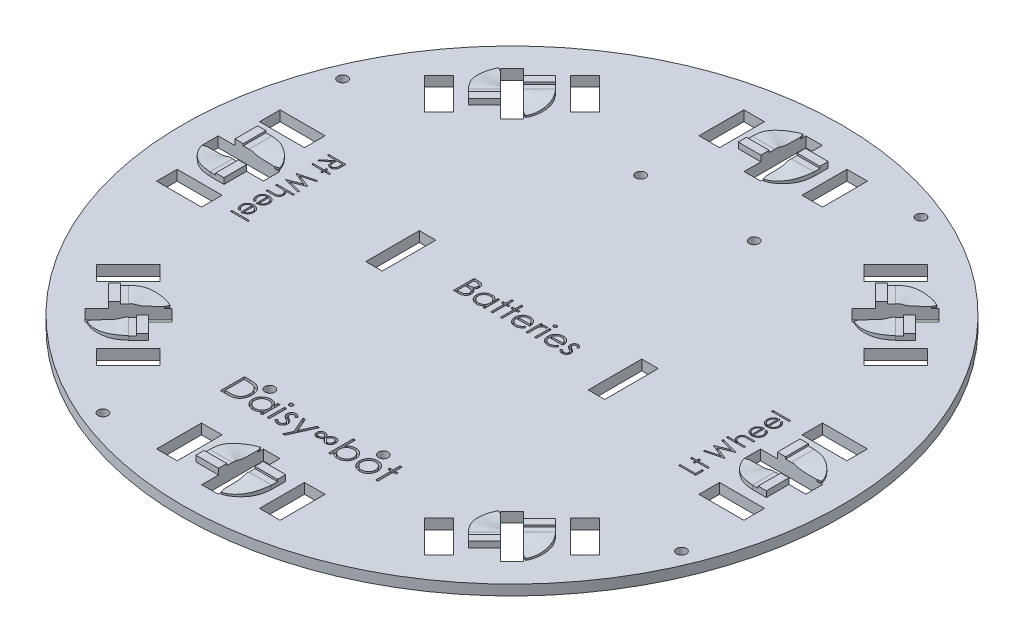
SolidWorks part; units mm, degrees
ref_plane "Front" through (0, 0, 0) normal (0, 0, 1) x (1, 0, 0)
ref_plane "Top" through (0, 0, 0) normal (0, 1, 0) x (1, 0, 0)
ref_plane "Right" through (0, 0, 0) normal (1, 0, 0) x (0, 0, -1)
sketch "Sketch1" plane through (0, 0, 0) normal (0, 1, 0) x (1, 0, 0)
  circle A0 centre (0, 0) radius 101.6
  dimension "D1" = 203.2
extrude "Boss-Extrude1" add sketch "Sketch1" along normal blind 3.175 contours A0
sketch "Sketch2" plane through (0, 3.175, 0) normal (0, 1, 0) x (1, 0, 0)
  line L1 (-2.54, -93.1333) -> (2.54, -93.1333)
  line L2 (-2.54, -93.1333) -> (-2.54, -74.0833)
  line L3 (-2.54, -74.0833) -> (2.54, -74.0833)
  line L4 (2.54, -93.1333) -> (2.54, -74.0833)
  circle A0 centre (0, 0) radius 101.6 construction
  point P4 (0, -74.0833)
  dimension "D1" = 5.08
  dimension "D2" = 19.05
  dimension "D3" = 93.1333
extrude "Cut-Extrude1" cut sketch "Sketch2" against normal up to next and the other way through all contours L1 L4 L3 L2
sketch "Sketch4" plane through (0, 3.175, 0) normal (0, 1, 0) x (1, 0, 0)
  line L0 (0, -83.6083) -> (-2.9434, -74.5495) construction
  line L1 (-2.9434, -74.5495) -> (0, -83.6083) construction
  line L2 (0, -83.6083) -> (-5.5987, -75.9025) construction
  line L3 (0, -83.6083) -> (-7.7059, -78.0097) construction
  line L4 (0, -83.6083) -> (-9.0588, -80.665) construction
  line L5 (0, -83.6083) -> (-9.525, -83.6083) construction
  line L9 (2.54, -74.0833) -> (-2.54, -74.0833) construction
  line L10 (2.54, -74.0833) -> (2.54, -93.1333) construction
  line L11 (-2.54, -74.0833) -> (-2.54, -93.1333) construction
  line L12 (2.54, -93.1333) -> (-2.54, -93.1333) construction
  circle A0 centre (0, -83.6083) radius 9.525 construction
  point P16 (0, -74.0833)
  point P19 (2.54, -83.6083)
  dimension "D1" = 18
  dimension "D2" = 18
  dimension "D3" = 18
  dimension "D4" = 18
  dimension "D5" = 18
ref_plane "Plane1" through (-24.5719, 0, 7.9839) normal (0.9511, 0, -0.309) x (-0.309, 0, -0.9511)
ref_plane "Plane2" through (-39.7581, 0, 28.886) normal (0.809, 0, -0.5878) x (-0.5878, 0, -0.809)
ref_plane "Plane3" through (-39.7581, 0, 54.7224) normal (0.5878, 0, -0.809) x (-0.809, 0, -0.5878)
ref_plane "Plane4" through (-24.5719, 0, 75.6245) normal (0.309, 0, -0.9511) x (-0.9511, 0, -0.309)
ref_plane "Plane5" through (0, 0, 83.6083) normal (0, 0, -1) x (-1, 0, 0)
sketch "Sketch5" plane through (-24.5719, 0, 7.9839) normal (0.9511, 0, -0.309) x (-0.309, 0, -0.9511)
  line L0 (-69.6725, 3.175) -> (-87.7902, 3.175) construction
  line L1 (-71.2966, 3.175) -> (-69.9913, 3.175)
  line L2 (-71.2966, 3.175) -> (-71.2966, 3.683)
  line L3 (-71.2966, 3.683) -> (-69.9913, 3.683)
  line L4 (-69.9913, 3.175) -> (-69.9913, 3.683)
  dimension "D2" = 0.508
sketch "Sketch6" plane through (-39.7581, 0, 28.886) normal (0.809, 0, -0.5878) x (-0.5878, 0, -0.809)
  line L0 (-58.4417, 3.175) -> (-73.8535, 3.175) construction
  line L1 (-63.3193, 3.175) -> (-58.1156, 3.175)
  line L2 (-63.3193, 3.175) -> (-63.3193, 3.775)
  line L3 (-63.3193, 3.775) -> (-58.1156, 3.775)
  line L4 (-58.1156, 3.175) -> (-58.1156, 3.775)
  dimension "D2" = 0.6
sketch "Sketch7" plane through (-39.7581, 0, 54.7224) normal (0.5878, 0, -0.809) x (-0.809, 0, -0.5878)
  line L0 (-41.4902, 3.175) -> (-52.6875, 3.175) construction
  line L1 (-46.0041, 3.175) -> (-39.6188, 3.175)
  line L2 (-46.0041, 3.175) -> (-46.0041, 4.075)
  line L3 (-46.0041, 4.075) -> (-39.6188, 4.075)
  line L4 (-39.6188, 3.175) -> (-39.6188, 4.075)
  dimension "D2" = 0.9
sketch "Sketch10" plane through (-24.5719, 0, 75.6245) normal (0.309, 0, -0.9511) x (-0.9511, 0, -0.309)
  line L0 (-25.8364, 3.175) -> (-16.7776, 3.175) construction
  line L1 (-23.1657, 3.175) -> (-16.3114, 3.175)
  line L2 (-23.1657, 3.175) -> (-23.1657, 4.375)
  line L3 (-23.1657, 4.375) -> (-16.3114, 4.375)
  line L4 (-16.3114, 3.175) -> (-16.3114, 4.375)
  dimension "D3" = 1.2
sketch "Sketch11" plane through (0, 0, 83.6083) normal (0, 0, -1) x (-1, 0, 0)
  line L0 (0, 3.175) -> (9.525, 3.175) construction
  line L1 (2.54, 3.175) -> (9.525, 3.175)
  line L2 (2.54, 3.175) -> (2.54, 4.375)
  line L3 (2.54, 4.375) -> (9.525, 4.375)
  line L4 (9.525, 3.175) -> (9.525, 4.375)
  dimension "D3" = 1.2
loft "Loft1" add profiles "Sketch5", "Sketch6", "Sketch7", "Sketch10", "Sketch11" connector at (-2.54, 3.683, 75.791) connector at (-2.54, 3.775, 80.1123) connector at (-2.54, 4.075, 81.7629) connector at (-2.54, 4.375, 82.783) connector at (-2.54, 4.375, 83.6083)
sketch "Sketch13" plane through (-104.9799, 0, 83.6083) normal (0, 0, -1) x (-1, 0, 0)
  line L6 (-95.4549, 3.175) -> (-102.4399, 3.175)
  line L7 (-95.4549, 3.175) -> (-95.4549, 4.375)
  line L8 (-95.4549, 4.375) -> (-102.4399, 4.375)
  line L9 (-102.4399, 3.175) -> (-102.4399, 4.375)
extrude "Boss-Extrude4" add sketch "Sketch13" against normal blind 1.7907
sketch "Sketch25" plane through (0, 0, 85.399) normal (0, 0, 1) x (1, 0, 0)
  line L0 (-9.525, 4.375) -> (-2.54, 4.375) construction
  line L1 (-9.525, 3.175) -> (-2.54, 3.175)
  line L2 (-9.525, 3.175) -> (-9.525, 4.975)
  line L3 (-9.525, 4.975) -> (-2.54, 4.975)
  line L4 (-2.54, 3.175) -> (-2.54, 4.975)
  dimension "D1" = 0.6
extrude "Boss-Extrude5" add sketch "Sketch25" along normal blind 2.54
sketch "Sketch14" plane through (-2.54, 0, 0) normal (1, 0, 0) x (0, 0, -1)
  line L0 (-83.6083, 3.175) -> (-83.6083, 0) construction
  line L1 (-74.0833, 0) -> (-93.1333, 0) construction
ref_plane "Plane6" through (0, 0, 0) normal (1, 0, 0) x (0, 0, -1)
sketch "Sketch15" plane through (0, 0, 0) normal (1, 0, 0) x (0, 0, -1)
  line L0 (-83.6083, 0) -> (-83.6083, 3.175) construction
pattern_circular "CirPattern1" count 2 over 360 about axis through (0, 0, 83.6083) along (0, 1, 0) of "Loft1", "Boss-Extrude5", "Boss-Extrude4" reverse direction yes
ref_axis "Axis1" through (0, 50, 0) along (0, -1, 0)
pattern_circular "CirPattern5" count 8 over 360 about axis through (0, 50, 0) along (0, -1, 0) of "CirPattern1", "Cut-Extrude1"
sketch "Sketch18" plane through (0, 3.175, 0) normal (0, 1, 0) x (1, 0, 0)
  line L4 (0, -101.6) -> (0, 101.6) construction
  line L5 (0, -1.7463) -> (0, 1.7463) construction
  line L6 (-101.6, 0) -> (101.6, 0) construction
  circle A8 centre (0, 0) radius 101.6 construction
sketch "Sketch19" plane through (0, 3.175, 0) normal (0, 1, 0) x (1, 0, 0)
  line L0 (-36.9366, -89.1729) -> (0, 0) construction
  line L1 (0, -101.6) -> (0, 101.6) construction
  circle A1 centre (-36.9366, -89.1729) radius 1.5
  dimension "D1" = 96.52
  dimension "D4" = 3
  dimension "D5" = 22.5
extrude "Cut-Extrude2" cut sketch "Sketch19" against normal through all
pattern_circular "CirPattern7" count 4 over 360 about axis through (0, 50, 0) along (0, -1, 0) of "Cut-Extrude2"
sketch "Sketch23" plane through (0, 3.175, 0) normal (0, 1, 0) x (1, 0, 0)
  line L9 (-2.54, -87.939) -> (-2.54, -93.1333) construction
  line L10 (-19.05, -76.6805) -> (-12.7, -76.6805)
  line L11 (-19.05, -76.6805) -> (-19.05, -90.5362)
  line L16 (-19.05, -90.5362) -> (-12.7, -90.5362)
  line L17 (-12.7, -76.6805) -> (-12.7, -90.5362)
  line L19 (2.54, -74.0833) -> (2.54, -79.2776) construction
  line L20 (0, -50) -> (0, 50) construction
  line L21 (12.7, -76.6805) -> (12.7, -90.5362)
  line L22 (19.05, -90.5362) -> (12.7, -90.5362)
  line L23 (19.05, -76.6805) -> (19.05, -90.5362)
  line L24 (19.05, -76.6805) -> (12.7, -76.6805)
  point P8 (-2.54, -90.5362)
  point P9 (2.54, -76.6805)
  dimension "D1" = 6.35
  dimension "D2" = 10.16
extrude "Cut-Extrude6" cut sketch "Sketch23" against normal through all
pattern_circular "CirPattern8" count 8 over 360 about axis through (0, 50, 0) along (0, -1, 0) of "Cut-Extrude6"
sketch "Sketch16" plane through (0, 3.175, 0) normal (0, 1, 0) x (1, 0, 0)
  line L1 (-16.4163, -2.4279) -> (16.4163, -2.4279) construction
  line L2 (0, -101.6) -> (0, 101.6) construction
  line L3 (-71.12, 15.3104) -> (-71.12, -15.3104) construction
  line L4 (-101.6, 0) -> (101.6, 0) construction
  line L5 (71.12, 15.3104) -> (71.12, -15.3104) construction
  line L6 (-25.719, -65.1065) -> (25.719, -65.1065) construction
  circle A1 centre (0, 0) radius 101.6 construction
  text T0 "Daisy∞bot\r\n" font "Century Gothic" height in points 28
  text T1 "Batteries"
  text T2 "Rt Wheel\r\n" font "Century Gothic" height in points 20
  text T3 "Lt Wheel" font "Century Gothic" height in points 20
  point P4 (-71.12, 0)
  point P7 (0, -65.1065)
  point P10 (0, -2.4279)
  point P15 (71.12, 0)
  dimension "D1" = 32.8326
  dimension "D2" = 30.6207
  dimension "D3" = 51.438
  dimension "D4" = 71.12
  dimension "D5" = 71.12
extrude "Cut-Extrude4" cut sketch "Sketch16" against normal blind 1.27
sketch "Sketch26" plane through (0, 3.175, 0) normal (0, 1, 0) x (1, 0, 0)
  line L0 (-101.6, 0) -> (101.6, 0) construction
  line L1 (-36.83, 8.255) -> (-31.75, 8.255)
  line L2 (-36.83, 8.255) -> (-36.83, -8.255)
  line L3 (-36.83, -8.255) -> (-31.75, -8.255)
  line L4 (-31.75, 8.255) -> (-31.75, -8.255)
  line L5 (0, -101.6) -> (0, 101.6) construction
  point P4 (-36.83, 0)
  dimension "D1" = 16.51
  dimension "D2" = 5.08
  dimension "D3" = 31.75
extrude "Cut-Extrude7" cut sketch "Sketch26" against normal through all
mirror "Mirror1" about plane through (0, 0, 0) normal (1, 0, 0) of "Cut-Extrude7"
sketch "Sketch27" plane through (0, 0, 0) normal (0, -1, 0) x (1, 0, 0)
  line L0 (0, 101.6) -> (0, -101.6) construction
  line L1 (-101.6, 0) -> (101.6, 0) construction
  circle A0 centre (-17.5, -57.15) radius 1.5
  circle A1 centre (-89.1729, -36.9366) radius 1.5 construction
  dimension "D1" = 17.5
  dimension "D2" = 57.15
extrude "Cut-Extrude8" cut sketch "Sketch27" against normal through all both and the other way through all
mirror "Mirror2" about plane through (0, 0, 0) normal (0, 0, 1) of "Cut-Extrude8"
mirror "Mirror3" about plane through (0, 0, 0) normal (1, 0, 0) of "Mirror2"
sketch "Sketch28" plane through (0, 0, 0) normal (0, -1, 0) x (1, 0, 0)
  line L0 (-21.8435, -50.8) -> (21.8435, -50.8) construction
  line L1 (0, 101.6) -> (0, -101.6) construction
  line L2 (-101.6, 0) -> (101.6, 0) construction
  line L3 (-19.568, 50.8) -> (19.568, 50.8) construction
  text T0 "Bk Caster"
  text T1 "Ft Caster"
  point P3 (0, 50.8)
  point P4 (0, -50.8)
  dimension "D1" = 50.8
  dimension "D2" = 50.8
extrude "Cut-Extrude9" cut sketch "Sketch28" against normal blind 1.27
